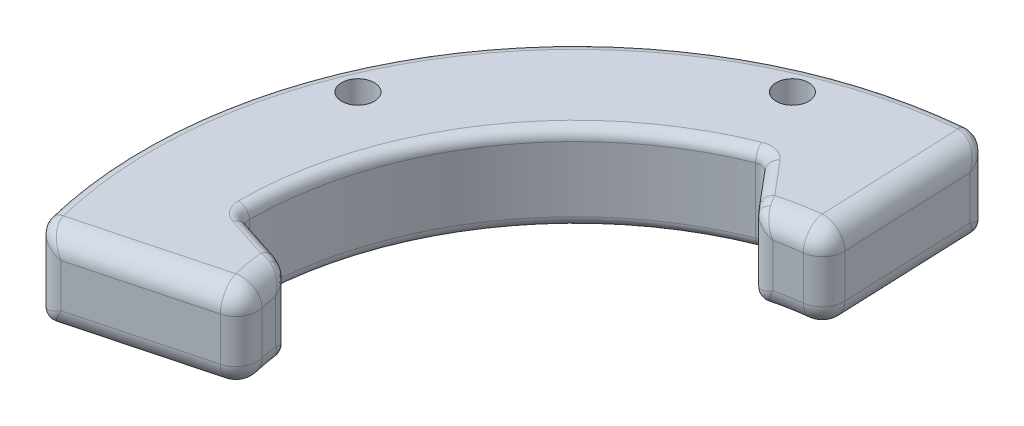
SolidWorks part; units mm, degrees
ref_plane "前视基准面" through (0, 0, 0) normal (0, 0, 1) x (1, 0, 0)
ref_plane "上视基准面" through (0, 0, 0) normal (0, 1, 0) x (1, 0, 0)
ref_plane "右视基准面" through (0, 0, 0) normal (1, 0, 0) x (0, 0, -1)
other "Configuration Table"
sketch "草图1" plane through (0, 0, 0) normal (0, 1, 0) x (1, 0, 0)
  line L6 (-29.9901, -0.7702) -> (-23.8398, -2.7686)
  line L7 (-10.5203, 28.0949) -> (-6.3635, 23.141)
  line L11 (-22.8319, -7.3961) -> (-38.3137, -11.4916)
  line L13 (-0.9668, 23.9805) -> (-1.6114, 39.9675)
  arc A41 (-1.6114, 39.9675) -> (-38.3137, -11.4916) centre (0, 0) ccw
  circle A47 centre (-34.1835, 14.1593) radius 1.5
  circle A48 centre (-14.1593, 34.1835) radius 1.5
  arc A52 (-10.5203, 28.0949) -> (-29.9901, -0.7702) centre (0, 0) ccw
  arc A54 (-0.9668, 23.9805) -> (-6.3635, 23.141) centre (0, 0) ccw
  arc A55 (-23.8398, -2.7686) -> (-22.8319, -7.3961) centre (0, 0) ccw
  point P21 (0, 0)
extrude "凸台-拉伸1" add sketch "草图1" along normal blind 8
fillet "圆角2" radius 2 14 edges at (-23.4503, 8, 5.1073) (-23.8398, 4, 2.7686) (-23.4503, 0, 5.1073) (-6.3635, 4, -23.141) (-3.6891, 8, -23.7148) (-3.6891, 0, -23.7148) (-0.9668, 4, -23.9805) (-1.2891, 8, -31.974) (-1.2891, 0, -31.974) (-1.6114, 4, -39.9675) (-38.3137, 4, 11.4916) (-30.5728, 8, 9.4439) (-22.8319, 4, 7.3961) (-30.5728, 0, 9.4439)
fillet "圆角3" radius 1 26 edges at (-2.171, 0.5858, -39.306) (-3.6602, 0, -39.8315) (-37.912, 0.5858, 10.7794) (-38.8445, 0, 9.5445) (-2.171, 7.4142, -39.306) (-3.6602, 8, -39.8315) (-37.912, 7.4142, 10.7794) (-38.8445, 8, 9.5445) (-32.5858, 0, -23.1984) (-32.5858, 8, -23.1984) (-24.4421, 7.4178, 2.6869) (-24.4421, 0.5822, 2.6869) (-6.665, 7.4178, -23.6689) (-6.665, 0.5822, -23.6689) (-25.1809, 7.8692, 2.3329) (-25.7497, 0.0065, 2.148) (-7.6544, 7.9935, -24.6794) (-7.2699, 0.1308, -24.2212) (-27.9528, 8, 1.4322) (-27.9528, 0, 1.4322) (-9.1434, 8, -26.4539) (-9.1434, 0, -26.4539) (-29.9901, 4, 0.7702) (-24.8711, 8, -16.7758) (-10.5203, 4, -28.0949) (-24.8711, 0, -16.7758)
